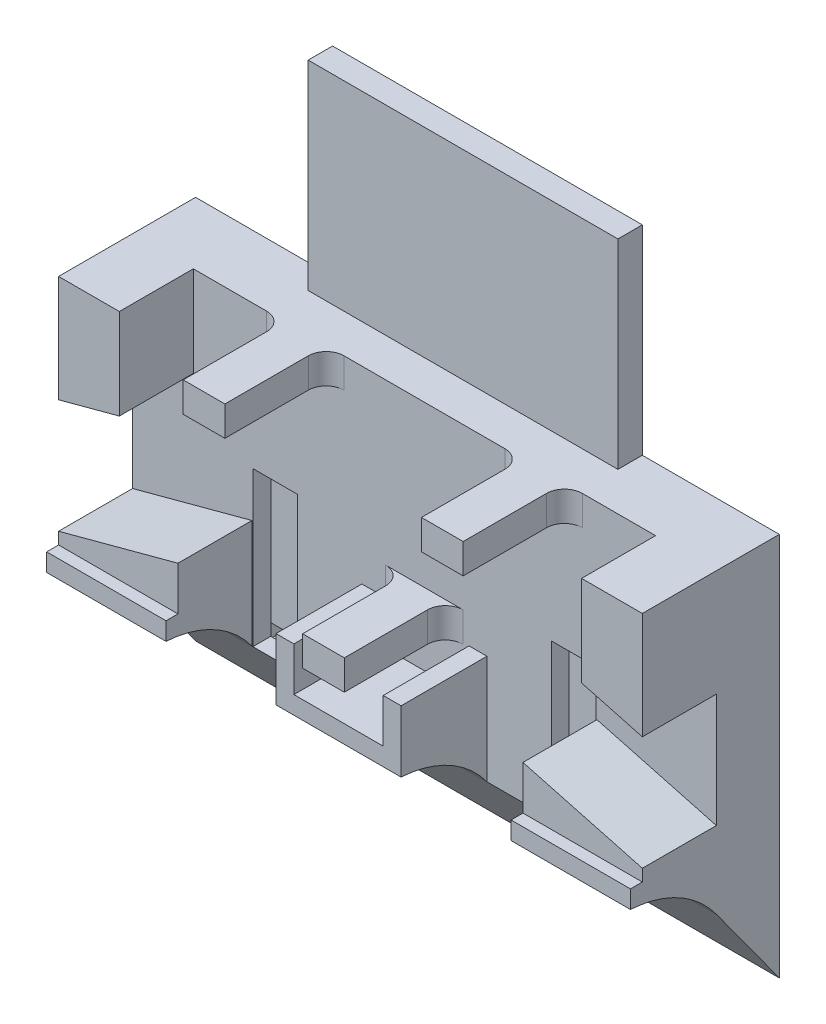
SolidWorks part; units mm, degrees
material "1060-H16"
ref_plane "Alzado" through (0, 0, 0) normal (0, 0, 1) x (1, 0, 0)
ref_plane "Planta" through (0, 0, 0) normal (0, 1, 0) x (1, 0, 0)
ref_plane "Vista lateral" through (0, 0, 0) normal (1, 0, 0) x (0, 0, -1)
other "Centro de masa"
sketch "Croquis1" plane through (0, 0, 0) normal (0, 0, 1) x (1, 0, 0)
  line L1 (-49, 49) -> (49, 49)
  line L2 (-49, 49) -> (-49, -49)
  line L3 (-49, -49) -> (49, -49)
  line L4 (49, 49) -> (49, -49)
  line L5 (-49, 49) -> (49, -49) construction
  line L6 (-49, -49) -> (49, 49) construction
  point P0 (0, 0)
  dimension "D1" = 98
  dimension "D2" = 98
extrude "Saliente-Extruir2" add sketch "Croquis1" along normal blind 25 contours L4 L3 L2 L1
sketch "Croquis3" plane through (49, 0, 0) normal (1, 0, 0) x (0, 0, -1)
  line L0 (0, -49) -> (-10.5801, -34.4377)
  line L1 (-25, 49) -> (-25, -49) construction
  line L2 (0, 49) -> (0, -49) construction
  line L3 (0, -49) -> (-10.5801, -34.4377) construction
  line L4 (0, -49) -> (-25, -49)
  line L5 (-25, -49) -> (-25, -26.5445)
  arc A0 (-10.5801, -34.4377) -> (-25, -26.5445) centre (-26.1375, -45.7408) ccw
  dimension "D3" = 38.46
  dimension "D1" = 36
  dimension "D2" = 18
extrude "Cortar-Extruir1" cut sketch "Croquis3" against normal through all
sketch "Croquis4" plane through (0, 0, 25) normal (0, 0, 1) x (1, 0, 0)
  line L0 (0, 0) -> (0, 24.7831) construction
  line L1 (-49, 49) -> (-26, 49)
  line L2 (-49, 49) -> (-49, 14)
  line L3 (-49, 14) -> (-26, 14)
  line L4 (-26, 49) -> (-26, 14)
  line L5 (49, 14) -> (26, 14)
  line L6 (26, 49) -> (26, 14)
  line L7 (49, 49) -> (26, 49)
  line L8 (49, 49) -> (49, 14)
  dimension "D1" = 35
  dimension "D2" = 23
extrude "Cortar-Extruir2" cut sketch "Croquis4" against normal through all
sketch "Croquis5" plane through (0, 0, 25) normal (0, 0, 1) x (1, 0, 0)
  line L1 (-26, 49) -> (26, 49)
  line L2 (-26, 49) -> (-26, 14)
  line L3 (-26, 14) -> (26, 14)
  line L4 (26, 49) -> (26, 14)
extrude "Cortar-Extruir3" cut sketch "Croquis5" against normal blind 20
sketch "Croquis6" plane through (0, 0, 25) normal (0, 0, 1) x (1, 0, 0)
  line L0 (-49, -34.4377) -> (49, -34.4377) construction
  line L1 (-28.8, -34.4377) -> (-10.5, -34.4377)
  line L2 (-28.8, -34.4377) -> (-28.8, -23.5445)
  line L3 (-28.8, -23.5445) -> (-10.5, -23.5445)
  line L4 (-10.5, -34.4377) -> (-10.5, -23.5445)
  line L5 (0, 0) -> (0, -26.5445) construction
  line L6 (-49, -26.5445) -> (49, -26.5445) construction
  line L7 (-49, -23.5445) -> (49, -23.5445)
  line L8 (-49, 14) -> (-49, -26.5445) construction
  line L9 (49, 14) -> (49, -26.5445) construction
  line L10 (28.8, -23.5445) -> (10.5, -23.5445)
  line L11 (10.5, -34.4377) -> (10.5, -23.5445)
  line L12 (28.8, -34.4377) -> (10.5, -34.4377)
  line L13 (28.8, -34.4377) -> (28.8, -23.5445)
  dimension "D1" = 18.3
  dimension "D2" = 10.5
  dimension "D3" = 3
extrude "Cortar-Extruir4" cut sketch "Croquis6" against normal up to vertex (14.4199 mm away) contours L2 L1 L4 L3 | L10 L11 L12 L13 up to point (-49, -34.4377, 10.5801)
sketch "Croquis7" plane through (0, 0, 25) normal (0, 0, 1) x (1, 0, 0)
  line L0 (28.8, -26.5445) -> (28.8, -34.4377) construction
  line L1 (-28.8, -23.5445) -> (28.8, -23.5445)
  line L2 (-28.8, -23.5445) -> (-28.8, 14)
  line L3 (-28.8, 14) -> (28.8, 14)
  line L4 (28.8, -23.5445) -> (28.8, 14)
  line L5 (-26, 14) -> (26, 14) construction
extrude "Cortar-Extruir5" cut sketch "Croquis7" against normal up to vertex (14.4199 mm away) up to point (-28.8, -34.4377, 10.5801)
sketch "Croquis8" plane through (0, 0, 25) normal (0, 0, 1) x (1, 0, 0)
  line L0 (-10.5, -23.5445) -> (10.5, -23.5445) construction
  line L1 (49, -23.5445) -> (-49, -23.5445)
  line L2 (49, -23.5445) -> (49, 14)
  line L3 (49, 14) -> (-49, 14)
  line L4 (-49, -23.5445) -> (-49, 14)
  line L5 (-10.5, -23.5445) -> (10.5, -23.5445) construction
extrude "Cortar-Extruir6" cut sketch "Croquis8" against normal blind 2
sketch "Croquis9" plane through (0, 0, 23) normal (0, 0, 1) x (1, 0, 0)
  line L0 (49, -23.5445) -> (49, -21.5445)
  line L1 (49, -23.5445) -> (49, 14) construction
  line L2 (49, -21.5445) -> (28.8, -16.1319)
  line L3 (28.8, -34.4377) -> (28.8, 14) construction
  line L4 (49, -3.2445) -> (28.8, 2.1681)
  line L5 (28.8, -16.1319) -> (28.8, 2.1681)
  line L6 (49, -3.2445) -> (49, -21.5445)
  line L7 (0, 0) -> (0, -14.0754) construction
  line L8 (-49, -3.2445) -> (-49, -21.5445)
  line L9 (-49, -3.2445) -> (-28.8, 2.1681)
  line L10 (-28.8, -16.1319) -> (-28.8, 2.1681)
  line L11 (-49, -21.5445) -> (-28.8, -16.1319)
  line M7 (28.8, 14) -> (28.8, -23.5445)
  line M9 (49, -23.5445) -> (49, 14)
  dimension "D1" = 2
  dimension "D2" = 105
  dimension "D3" = 18.3
extrude "Cortar-Extruir7" cut sketch "Croquis9" against normal up to vertex (12.4199 mm away) contours L8 L11 L10 L9 | L4 L2 M9 M7 region at (38.9, -9.6882, 23) region at (-38.9, -9.6882, 23) up to point (-28.8, -34.4377, 10.5801)
sketch "Croquis10" plane through (0, 0, 23) normal (0, 0, 1) x (1, 0, 0)
  line L0 (-49, -3.2445) -> (-28.8, 2.1681) construction
  line L1 (-28.8, 14) -> (-38.8, 14)
  line L2 (-28.8, 14) -> (-28.8, -0.5114)
  line L3 (-28.8, -0.5114) -> (-38.8, -0.5114)
  line L4 (-38.8, 14) -> (-38.8, -0.5114)
  line L5 (0, 0) -> (0, -10.5483) construction
  line L6 (28.8, -0.5114) -> (38.8, -0.5114)
  line L7 (38.8, 14) -> (38.8, -0.5114)
  line L8 (28.8, 14) -> (38.8, 14)
  line L9 (28.8, 14) -> (28.8, -0.5114)
  dimension "D1" = 10
extrude "Cortar-Extruir8" cut sketch "Croquis10" against normal up to vertex (12.4199 mm away) up to point (-10.5, -34.4377, 10.5801)
sketch "Croquis11" plane through (28.8, 0, 0) normal (-1, 0, 0) x (0, 0, 1)
  line L0 (25, -26.5445) -> (4.5573, -26.5445) construction
sketch "Croquis12" plane through (-28.8, 0, 0) normal (1, 0, 0) x (0, 0, -1)
  line L0 (-25, -26.5445) -> (-6.7401, -26.5445) construction
  line L1 (-25, -26.5445) -> (-4.5573, -26.5445) construction
sketch "Croquis13" plane through (0, 0, 10.5801) normal (0, 0, 1) x (1, 0, 0)
  line L0 (-49, -26.5445) -> (-28.8, -26.5445) construction
  line L1 (-28.8, -34.4377) -> (-21.3, -34.4377)
  line L2 (-28.8, -34.4377) -> (-28.8, -8.5445)
  line L3 (-28.8, -8.5445) -> (-21.3, -8.5445)
  line L4 (-21.3, -34.4377) -> (-21.3, -8.5445)
  line L5 (0, -23.5445) -> (0, -7.4948) construction
  line L6 (-10.5, -23.5445) -> (10.5, -23.5445) construction
  line L7 (28.8, -8.5445) -> (21.3, -8.5445)
  line L8 (21.3, -34.4377) -> (21.3, -8.5445)
  line L9 (28.8, -34.4377) -> (21.3, -34.4377)
  line L10 (28.8, -34.4377) -> (28.8, -8.5445)
  dimension "D1" = 7.5
  dimension "D2" = 18
extrude "Cortar-Extruir9" cut sketch "Croquis13" against normal blind 3
sketch "Croquis16" plane through (0, 0, 7.5801) normal (0, 0, 1) x (1, 0, 0)
  line L0 (-28.8, -34.4377) -> (-28.8, -26.5445) construction
  line L1 (-21.3, -34.4377) -> (-28.8, -34.4377)
  line L2 (-21.3, -34.4377) -> (-21.3, -32.4377)
  line L3 (-21.3, -32.4377) -> (-28.8, -32.4377)
  line L4 (-28.8, -34.4377) -> (-28.8, -32.4377)
  line L5 (21.3, -8.5445) -> (21.3, -34.4377) construction
  line L6 (28.8, -34.4377) -> (21.3, -34.4377)
  line L7 (28.8, -34.4377) -> (28.8, -32.4377)
  line L8 (28.8, -32.4377) -> (21.3, -32.4377)
  line L9 (21.3, -34.4377) -> (21.3, -32.4377)
  dimension "D1" = 2
  dimension "D2" = 2
extrude "Cortar-Extruir10" cut sketch "Croquis16" against normal through all
sketch "Croquis17" plane through (0, 0, 0) normal (0, 0, -1) x (-1, 0, 0)
  line L0 (49, -49) -> (-49, -49) construction
  line L1 (-46, -44.7) -> (-21.3, -44.7)
  line L2 (-46, -44.7) -> (-46, -37)
  line L3 (-46, -37) -> (-28.8, -37)
  line L4 (-21.3, -44.7) -> (-21.3, -37)
  line L5 (-49, 14) -> (-49, -49) construction
  line L6 (-21.3, -32.4377) -> (-21.3, -34.4377) construction
  line L7 (0, 0) -> (0, -19.2755) construction
  line L8 (46, -44.7) -> (21.3, -44.7)
  line L10 (-21.3, -37) -> (-21.3, -34.4377)
  line L11 (-21.3, -34.4377) -> (-28.8, -34.4377)
  line L12 (-28.8, -37) -> (-28.8, -34.4377)
  line L13 (21.3, -44.7) -> (21.3, -37)
  line L14 (21.3, -37) -> (21.3, -34.4377)
  line L15 (21.3, -34.4377) -> (28.8, -34.4377)
  line L16 (28.8, -37) -> (28.8, -34.4377)
  line L17 (46, -37) -> (28.8, -37)
  line L18 (46, -44.7) -> (46, -37)
  dimension "D1" = 7.7
  dimension "D2" = 4.3
  dimension "D3" = 3
extrude "Cortar-Extruir11" cut sketch "Croquis17" against normal blind 3
ref_plane "Plano1" through (0, 0, 0) normal (0, 0, -1) x (-1, 0, 0)
sketch "Croquis21" plane through (0, 14, 0) normal (0, 1, 0) x (1, 0, 0)
  line L0 (-49, 0) -> (-49, -23)
  line L1 (53.9, 0) -> (-53.9, 0) construction
  line L2 (-49, 0) -> (-49, -23) construction
  line L3 (-49, -23) -> (-38.8, -23)
  line L4 (-38.8, -23) -> (-38.8, -10.5801)
  line L5 (-38.8, -10.5801) -> (38.8, -10.5801)
  line L6 (38.8, -10.5801) -> (38.8, -23)
  line L7 (38.8, -23) -> (49, -23)
  line L8 (49, -23) -> (49, 0)
  line L9 (49, 0) -> (26, 0)
  line L10 (26, 0) -> (26, -5)
  line L11 (26, -5) -> (-26, -5)
  line L12 (-26, -5) -> (-26, 0)
  line L13 (-26, 0) -> (-49, 0)
extrude "Saliente-Extruir4" add sketch "Croquis21" along normal blind 1.5
sketch "Croquis24" plane through (0, 0, 5) normal (0, 0, 1) x (1, 0, 0)
  line L1 (-26, 49) -> (26, 49)
  line L2 (-26, 49) -> (-26, 15.5)
  line L3 (-26, 15.5) -> (26, 15.5)
  line L4 (26, 49) -> (26, 15.5)
extrude "Saliente-Extruir7" add sketch "Croquis24" along normal blind 1.1
sketch "Croquis25" plane through (0, 0, 25) normal (0, 0, 1) x (1, 0, 0)
  line L0 (49, -21.5445) -> (28.8, -16.1319) construction
  line L1 (28.8, -34.4377) -> (28.96, -34.4377)
  line L2 (28.8, -34.4377) -> (28.8, -16.1319)
  line L3 (28.8, -16.1319) -> (28.96, -16.1319)
  line L4 (28.96, -34.4377) -> (28.96, -16.1319)
  line L6 (0, 0) -> (0, -14.6417) construction
  line L7 (-28.8, -16.1319) -> (-28.96, -16.1319)
  line L8 (-28.96, -34.4377) -> (-28.96, -16.1319)
  line L9 (-28.8, -34.4377) -> (-28.96, -34.4377)
  line L10 (-28.8, -34.4377) -> (-28.8, -16.1319)
  dimension "D1" = 0.16
extrude "Cortar-Extruir12" cut sketch "Croquis25" against normal up to vertex (14.4199 mm away) up to point (-28.8, -34.4377, 10.5801)
sketch "Croquis26" plane through (0, 0, 25) normal (0, 0, 1) x (1, 0, 0)
  line L0 (0, 0) -> (0, -14.3536) construction
  line L1 (-10.5, -23.5445) -> (-7.5, -23.5445)
  line L2 (-10.5, -23.5445) -> (-10.5, -16.1748)
  line L3 (-10.5, -16.1748) -> (-7.5, -16.1748)
  line L4 (-7.5, -23.5445) -> (-7.5, -16.1748)
  line L5 (10.5, -16.1748) -> (7.5, -16.1748)
  line L6 (7.5, -23.5445) -> (7.5, -16.1748)
  line L7 (10.5, -23.5445) -> (7.5, -23.5445)
  line L8 (10.5, -23.5445) -> (10.5, -16.1748)
  dimension "D1" = 3
extrude "Saliente-Extruir8" add sketch "Croquis26" against normal up to vertex (14.4199 mm away) up to point (10.5, -23.5445, 10.5801)
sketch "Croquis27" plane through (0, 0, 23) normal (0, 0, 1) x (1, 0, 0)
  line L0 (49, -3.0788) -> (38.8, -0.3458)
  line L1 (49, -3.2445) -> (49, 15.5) construction
  line L2 (38.8, -0.5114) -> (38.8, 15.5) construction
  line L3 (49, -3.2445) -> (38.8, -0.5114) construction
  line L4 (38.8, -0.3458) -> (38.8, -0.5114)
  line L5 (38.8, -0.5114) -> (49, -3.2445)
  line L6 (49, -3.2445) -> (49, -3.0788)
  line L7 (0, 0) -> (0, -12.6078) construction
  line L8 (-38.8, -0.5114) -> (-49, -3.2445)
  line L9 (-38.8, -0.3458) -> (-38.8, -0.5114)
  line L10 (-49, -3.0788) -> (-38.8, -0.3458)
  line L11 (-49, -3.2445) -> (-49, -3.0788)
  dimension "D1" = 0.16
extrude "Cortar-Extruir13" cut sketch "Croquis27" against normal up to vertex (12.4199 mm away) up to point (49, -3.2445, 10.5801)
sketch "Croquis28" plane through (0, 0, 6.1) normal (0, 0, 1) x (1, 0, 0)
  line L1 (-26, 15.5) -> (26, 15.5)
  line L2 (-26, 15.5) -> (-26, 49)
  line L3 (-26, 49) -> (26, 49)
  line L4 (26, 15.5) -> (26, 49)
extrude "Cortar-Extruir14" cut sketch "Croquis28" against normal blind 2
sketch "Croquis29" plane through (0, 0, 0) normal (0, 0, -1) x (-1, 0, 0)
  line L0 (-46, -37) -> (-46, -44.7) construction
  line L1 (-21.3, -44.7) -> (-46, -44.7)
  line L2 (-21.3, -44.7) -> (-21.3, -41.7)
  line L3 (-21.3, -41.7) -> (-46, -41.7)
  line L4 (-46, -44.7) -> (-46, -41.7)
  line L5 (0, 0) -> (0, -25.6022) construction
  line L6 (21.3, -41.7) -> (46, -41.7)
  line L7 (46, -44.7) -> (46, -41.7)
  line L8 (21.3, -44.7) -> (46, -44.7)
  line L9 (21.3, -44.7) -> (21.3, -41.7)
  point P11 (0, 0)
  dimension "D1" = 3
extrude "Saliente-Extruir10" add sketch "Croquis29" against normal up to vertex (3 mm away) contours L2 L1 L4 L3 | L6 L7 L8 L9 up to point (21.3, -44.7, 3)
sketch "Croquis30" plane through (0, 0, 0) normal (0, 0, -1) x (-1, 0, 0)
  line L0 (-28.8, -37) -> (-28.8, -32.4377) construction
  line L1 (-46, -37) -> (-28.8, -37)
  line L2 (-46, -37) -> (-46, -33.9)
  line L3 (-46, -33.9) -> (-28.8, -33.9)
  line L4 (-28.8, -37) -> (-28.8, -33.9)
  line L5 (0, 0) -> (0, -20.7105) construction
  line L6 (46, -33.9) -> (28.8, -33.9)
  line L7 (28.8, -37) -> (28.8, -33.9)
  line L8 (46, -37) -> (28.8, -37)
  line L9 (46, -37) -> (46, -33.9)
  dimension "D1" = 3.1
extrude "Cortar-Extruir15" cut sketch "Croquis30" against normal up to vertex (3 mm away) up to point (21.3, -34.4377, 3)
ref_plane "Plano2" through (0, 15.5, 0) normal (0, 1, 0) x (1, 0, 0)
sketch "Croquis32" plane through (0, 15.5, 0) normal (0, 1, 0) x (1, 0, 0)
  line L0 (22, -13.5801) -> (22, -30.5801)
  line L1 (-38.8, -10.5801) -> (38.8, -10.5801) construction
  line L2 (22, -30.5801) -> (18, -30.5801)
  line L3 (18, -30.5801) -> (18, -13.5801)
  line L4 (0, 0) -> (0, -29.3248) construction
  line L5 (-25, -10.5801) -> (-15, -10.5801)
  line L6 (25, -10.5801) -> (15, -10.5801)
  line L7 (-22, -13.5801) -> (-22, -30.5801)
  line L8 (-22, -30.5801) -> (-18, -30.5801)
  line L9 (-18, -30.5801) -> (-18, -13.5801)
  arc A0 (25, -10.5801) -> (22, -13.5801) centre (25, -13.5801) ccw
  arc A1 (15, -10.5801) -> (18, -13.5801) centre (15, -13.5801) cw
  arc A2 (-25, -10.5801) -> (-22, -13.5801) centre (-25, -13.5801) cw
  arc A3 (-15, -10.5801) -> (-18, -13.5801) centre (-15, -13.5801) ccw
  point P10 (27.7662, -10.5801)
  point P13 (23.7662, -10.5801)
  dimension "D3" = 3
  dimension "D1" = 4
  dimension "D2" = 20
  dimension "D4" = 15
extrude "Saliente-Extruir11" add sketch "Croquis32" against normal blind 3
sketch "Croquis33" plane through (0, 15.5, 0) normal (0, 1, 0) x (1, 0, 0)
  line L0 (22, -30.5801) -> (22, -13.5801) construction
  line L1 (18, -30.5801) -> (22, -30.5801)
  line L2 (18, -30.5801) -> (18, -27.5801)
  line L3 (18, -27.5801) -> (22, -27.5801)
  line L4 (22, -30.5801) -> (22, -27.5801)
  line L5 (-18, -30.5801) -> (-18, -13.5801) construction
  line L6 (-22, -30.5801) -> (-18, -30.5801)
  line L7 (-22, -30.5801) -> (-22, -27.5801)
  line L8 (-22, -27.5801) -> (-18, -27.5801)
  line L9 (-18, -30.5801) -> (-18, -27.5801)
  dimension "D1" = 3
  dimension "D2" = 3
extrude "Cortar-Extruir16" cut sketch "Croquis33" against normal blind 3
sketch "Croquis34" plane through (0, 15.5, 0) normal (0, 1, 0) x (1, 0, 0)
  line L0 (0, 0) -> (0, -21.1603) construction
  line L1 (10.5, -10.5801) -> (7.5, -10.5801) construction
  line L2 (-15, -10.5801) -> (15, -10.5801) construction
  line L4 (-2, -13.5801) -> (-2, -27.5298)
  line L5 (-2, -27.5298) -> (2, -27.5298)
  line L6 (2, -13.5801) -> (2, -27.5298)
  line L11 (-5, -10.5801) -> (5, -10.5801)
  arc A0 (2, -13.5801) -> (5, -10.5801) centre (5, -13.5801) cw
  arc A1 (-2, -13.5801) -> (-5, -10.5801) centre (-5, -13.5801) ccw
  point P1 (0, -10.5801)
  point P17 (1.8902, -10.5812)
  point P20 (-1.9248, -10.5801)
  dimension "D2" = 3
  dimension "D1" = 16.949
  dimension "D3" = 4
  dimension "D4" = 2
extrude "Saliente-Extruir12" add sketch "Croquis34" against normal blind 3 from offset 22.94 offset against normal yes
sketch "Croquis35" plane through (0, 15.5, 0) normal (0, 1, 0) x (1, 0, 0)
  line L0 (-15, -10.5801) -> (15, -10.5801) construction
  line L1 (18, -27.5801) -> (16.5, -27.5801)
  line L2 (18, -27.5801) -> (18, -10.5801)
  line L4 (16.5, -27.5801) -> (16.5, -13.5801)
  line L5 (26.5, -10.5801) -> (22, -10.5801)
  line L6 (22, -27.5801) -> (23.5, -27.5801)
  line L7 (22, -27.5801) -> (22, -10.5801)
  line L9 (23.5, -27.5801) -> (23.5, -13.5801)
  line L10 (-38.8, -10.5801) -> (-25, -10.5801) construction
  line L11 (-18, -27.5801) -> (-16.5, -27.5801)
  line L12 (-18, -27.5801) -> (-18, -10.5801)
  line L14 (-16.5, -27.5801) -> (-16.5, -13.5801)
  line L15 (-22, -27.5801) -> (-23.5, -27.5801)
  line L16 (-22, -27.5801) -> (-22, -10.5801)
  line L18 (-23.5, -27.5801) -> (-23.5, -13.5801)
  line L19 (18, -10.5801) -> (13.5, -10.5801)
  line L20 (-13.5, -10.5801) -> (-18, -10.5801)
  line L21 (-13.5, -10.5801) -> (-12.5706, -10.5801)
  line L22 (-26.5, -10.5801) -> (-27.2077, -10.5801)
  line L23 (-22, -10.5801) -> (-26.5, -10.5801)
  arc A0 (23.5, -13.5801) -> (26.5, -10.5801) centre (26.5, -13.5801) cw
  arc A1 (13.5, -10.5801) -> (16.5, -13.5801) centre (13.5, -13.5801) cw
  arc A2 (-26.5, -10.5801) -> (-23.5, -13.5801) centre (-26.5, -13.5801) cw
  arc A3 (-13.5, -10.5801) -> (-16.5, -13.5801) centre (-13.5, -13.5801) ccw
  dimension "D5" = 3
  dimension "D6" = 3
  dimension "D7" = 3
  dimension "D1" = 1.5
  dimension "D2" = 1.5
  dimension "D3" = 1.5
  dimension "D4" = 1.5
extrude "Saliente-Extruir13" add sketch "Croquis35" against normal up to vertex (3 mm away) contours L9 A0 L5 L7 L6 | L19 A1 L4 L1 L2 | L23 A2 L18 L15 L16 | A3 L14 L11 L12 L20 region at (17.15, 15.5, 18.5288) region at (22.85, 15.5, 18.5288) region at (-22.85, 15.5, 18.5288) up to point (18, 12.5, 27.5801)
sketch "Croquis36" plane through (0, -7.44, 0) normal (0, 1, 0) x (1, 0, 0)
  line L1 (2, -27.5298) -> (3.5, -27.5298)
  line L2 (2, -27.5298) -> (2, -10.5801)
  line L4 (3.5, -27.5298) -> (3.5, -13.5801)
  line L6 (-2, -27.5298) -> (-3.5, -27.5298)
  line L7 (-2, -27.5298) -> (-2, -10.5801)
  line L9 (-3.5, -27.5298) -> (-3.5, -13.5801)
  line L11 (-7.5, -10.5801) -> (7.5, -10.5801) construction
  line L13 (-6.5, -10.5801) -> (-2, -10.5801)
  line L15 (6.5, -10.5801) -> (2, -10.5801)
  line L16 (-13.5, -10.5801) -> (13.5, -10.5801) construction
  arc A0 (-3.5, -13.5801) -> (-6.5, -10.5801) centre (-6.5, -13.5801) ccw
  arc A1 (3.5, -13.5801) -> (6.5, -10.5801) centre (6.5, -13.5801) cw
  dimension "D3" = 3
  dimension "D4" = 3
  dimension "D1" = 1.5
  dimension "D2" = 1.5
extrude "Saliente-Extruir14" add sketch "Croquis36" against normal up to vertex (3 mm away) up to point (-2, -10.44, 27.5298)
sketch "Croquis37" plane through (0, 0, 23) normal (0, 0, 1) x (1, 0, 0)
  line L0 (-49, -2.437) -> (-38.8, 0.2961)
  line L1 (-49, 15.5) -> (-49, -3.0788) construction
  line L2 (-38.8, 15.5) -> (-38.8, -0.3458) construction
  line L3 (-49, -21.5445) -> (-28.96, -16.1748) construction
  line L4 (-49, -2.437) -> (-49, -3.0788)
  line L5 (-49, -3.0788) -> (-38.8, -0.3458)
  line L6 (-38.8, -0.3458) -> (-38.8, 0.2961)
  line L8 (0, 0) -> (0, -5.797) construction
  line L9 (49, -3.0788) -> (38.8, -0.3458)
  line L10 (49, -2.437) -> (49, -3.0788)
  line L11 (49, -2.437) -> (38.8, 0.2961)
  line L12 (38.8, -0.3458) -> (38.8, 0.2961)
  dimension "D1" = 0.62
extrude "Cortar-Extruir17" cut sketch "Croquis37" against normal up to vertex (12.4199 mm away) up to point (-38.8, -0.3458, 10.5801)
sketch "Croquis39" plane through (0, 0, 0) normal (0, 0, -1) x (-1, 0, 0)
  line L1 (-28.8, -32.4377) -> (-21.3, -32.4377)
  line L2 (-28.8, -32.4377) -> (-28.8, -34.4377)
  line L3 (-28.8, -34.4377) -> (-21.3, -34.4377)
  line L4 (-21.3, -32.4377) -> (-21.3, -34.4377)
  line L5 (21.3, -32.4377) -> (28.8, -32.4377)
  line L6 (21.3, -32.4377) -> (21.3, -34.4377)
  line L7 (21.3, -34.4377) -> (28.8, -34.4377)
  line L8 (28.8, -32.4377) -> (28.8, -34.4377)
extrude "Saliente-Extruir15" add sketch "Croquis39" against normal up to vertex (7.5801 mm away) up to point (-21.3, -32.4377, 7.5801)
sketch "Croquis40" plane through (0, 0, 0) normal (0, 0, -1) x (-1, 0, 0)
  line L0 (21.3, -34.4377) -> (21.3, -41.7) construction
  line L1 (46, -41.7) -> (21.3, -41.7)
  line L2 (46, -41.7) -> (46, -39.7)
  line L3 (46, -39.7) -> (21.3, -39.7)
  line L4 (21.3, -41.7) -> (21.3, -39.7)
  line L5 (-46, -33.9) -> (-46, -41.7) construction
  line L6 (-21.3, -41.7) -> (-46, -41.7)
  line L7 (-21.3, -41.7) -> (-21.3, -39.7)
  line L8 (-21.3, -39.7) -> (-46, -39.7)
  line L9 (-46, -41.7) -> (-46, -39.7)
  dimension "D1" = 2
  dimension "D2" = 2
extrude "Saliente-Extruir16" add sketch "Croquis40" against normal up to vertex (3 mm away) up to point (21.3, -41.7, 3)
sketch "Croquis41" plane through (0, 0, 0) normal (0, 0, -1) x (-1, 0, 0)
  line L0 (-46, -33.9) -> (-46, -39.7) construction
  line L1 (-21.3, -34.4377) -> (-46, -34.4377)
  line L2 (-21.3, -34.4377) -> (-21.3, -32.4377)
  line L3 (-21.3, -32.4377) -> (-46, -32.4377)
  line L4 (-46, -34.4377) -> (-46, -32.4377)
  line L5 (46, -39.7) -> (46, -33.9) construction
  line L6 (21.3, -34.4377) -> (46, -34.4377)
  line L7 (21.3, -34.4377) -> (21.3, -32.4377)
  line L8 (21.3, -32.4377) -> (46, -32.4377)
  line L9 (46, -34.4377) -> (46, -32.4377)
  dimension "D1" = 2
  dimension "D2" = 2
extrude "Cortar-Extruir18" cut sketch "Croquis41" against normal up to vertex (3 mm away) up to point (-28.8, -34.4377, 3)
sketch "Croquis42" plane through (0, 0, 0) normal (0, 0, -1) x (-1, 0, 0)
  line L1 (21.3, -32.4377) -> (29, -32.4377)
  line L2 (21.3, -32.4377) -> (21.3, -34.9377)
  line L3 (21.3, -34.9377) -> (29, -34.9377)
  line L4 (29, -32.4377) -> (29, -34.9377)
  line L5 (-21.3, -32.4377) -> (-29, -32.4377)
  line L6 (-21.3, -32.4377) -> (-21.3, -34.9377)
  line L7 (-21.3, -34.9377) -> (-29, -34.9377)
  line L8 (-29, -32.4377) -> (-29, -34.9377)
  dimension "D1" = 2.5
  dimension "D2" = 7.7
  dimension "D3" = 2.5
  dimension "D4" = 7.7
extrude "Cortar-Extruir19" cut sketch "Croquis42" against normal up to vertex (7.5801 mm away) up to point (-21.3, -34.4377, 7.5801)
sketch "Croquis43" plane through (0, -7.44, 0) normal (0, 1, 0) x (1, 0, 0)
  line L1 (-3.5, -27.5298) -> (3.5, -27.5298)
  line L2 (-3.5, -27.5298) -> (-3.5, -13.5801)
  line L4 (3.5, -27.5298) -> (3.5, -13.5801)
  line L5 (3.5, -27.5298) -> (3.5, -13.5801) construction
  line L6 (-6.5, -10.5801) -> (6.5, -10.5801)
  arc A0 (-3.5, -13.5801) -> (-6.5, -10.5801) centre (-6.5, -13.5801) ccw
  arc A1 (6.5, -10.5801) -> (3.5, -13.5801) centre (6.5, -13.5801) ccw
  dimension "D1" = 3
  dimension "D2" = 3
extrude "Saliente-Extruir17" add sketch "Croquis43" against normal blind 5
sketch "Croquis44" plane through (3.5, 0, 0) normal (1, 0, 0) x (0, 0, -1)
  line L0 (-10.5801, -12.44) -> (-10.5801, -7.44) construction
  line L1 (-27.5298, -7.44) -> (-10.5801, -7.44)
  line L2 (-27.5298, -7.44) -> (-27.5298, -9.44)
  line L3 (-27.5298, -9.44) -> (-10.5801, -9.44)
  line L4 (-10.5801, -7.44) -> (-10.5801, -9.44)
  dimension "D1" = 2
extrude "Cortar-Extruir20" cut sketch "Croquis44" against normal mid plane 25
sketch "Croquis45" plane through (0, 0, 0) normal (0, 0, -1) x (-1, 0, 0)
  line L1 (-46, -32.4377) -> (-21.3, -32.4377)
  line L2 (-46, -32.4377) -> (-46, -31.8977)
  line L3 (-46, -31.8977) -> (-21.3, -31.8977)
  line L4 (-21.3, -32.4377) -> (-21.3, -31.8977)
  line L5 (-21.3, -39.7) -> (-21.3, -34.9377) construction
  line L6 (0, 0) -> (0, -18.3285) construction
  line L7 (46, -31.8977) -> (21.3, -31.8977)
  line L8 (21.3, -32.4377) -> (21.3, -31.8977)
  line L9 (46, -32.4377) -> (21.3, -32.4377)
  line L10 (46, -32.4377) -> (46, -31.8977)
  dimension "D1" = 0.54
extrude "Cortar-Extruir21" cut sketch "Croquis45" against normal up to vertex (3 mm away) up to point (29, -32.4377, 3)
sketch "Croquis47" plane through (0, 15.5, 0) normal (0, 1, 0) x (1, 0, 0)
  line L1 (-23.5, -27.5801) -> (-16.5, -27.5801)
  line L2 (-23.5, -27.5801) -> (-23.5, -13.5801)
  line L4 (-16.5, -27.5801) -> (-16.5, -13.5801)
  line L5 (-16.5, -27.5801) -> (-16.5, -13.5801) construction
  line L6 (0, 0) -> (0, -3.1555) construction
  line L8 (16.5, -27.5801) -> (16.5, -13.5801)
  line L9 (23.5, -27.5801) -> (16.5, -27.5801)
  line L10 (23.5, -27.5801) -> (23.5, -13.5801)
  line L11 (13.5, -10.5801) -> (26.5, -10.5801)
  line L17 (-26.5, -10.5801) -> (-13.5, -10.5801)
  arc A0 (23.5, -13.5801) -> (26.5, -10.5801) centre (26.5, -13.5801) cw
  arc A1 (16.5, -13.5801) -> (13.5, -10.5801) centre (13.5, -13.5801) ccw
  arc A2 (-16.5, -13.5801) -> (-13.5, -10.5801) centre (-13.5, -13.5801) cw
  arc A3 (-23.5, -13.5801) -> (-26.5, -10.5801) centre (-26.5, -13.5801) ccw
  dimension "D1" = 3
extrude "Saliente-Extruir18" add sketch "Croquis47" against normal blind 2 from offset 3 offset against normal yes
sketch "Croquis48" plane through (0, -9.44, 0) normal (0, 1, 0) x (1, 0, 0)
  line L1 (3.5, -27.5298) -> (-3.5, -27.5298)
  line L2 (3.5, -27.5298) -> (3.5, -13.5801)
  line L4 (-3.5, -27.5298) -> (-3.5, -13.5801)
  line L5 (-3.5, -13.5801) -> (-3.5, -27.5298) construction
  line L10 (-6.5, -10.5801) -> (6.5, -10.5801)
  arc A0 (-3.5, -13.5801) -> (-6.5, -10.5801) centre (-6.5, -13.5801) ccw
  arc A1 (3.5, -13.5801) -> (6.5, -10.5801) centre (6.5, -13.5801) cw
  dimension "D1" = 3
  dimension "D2" = 3
extrude "Saliente-Extruir19" add sketch "Croquis48" against normal blind 4 from offset 3 offset against normal yes
sketch "Croquis49" plane through (3.5, 0, 0) normal (1, 0, 0) x (0, 0, -1)
  line L0 (-10.5801, -16.44) -> (-10.5801, -9.44) construction
  line L1 (-27.5298, -9.44) -> (-10.5801, -9.44)
  line L2 (-27.5298, -9.44) -> (-27.5298, -11.44)
  line L3 (-27.5298, -11.44) -> (-10.5801, -11.44)
  line L4 (-10.5801, -9.44) -> (-10.5801, -11.44)
  dimension "D1" = 2
extrude "Cortar-Extruir22" cut sketch "Croquis49" against normal mid plane 25
